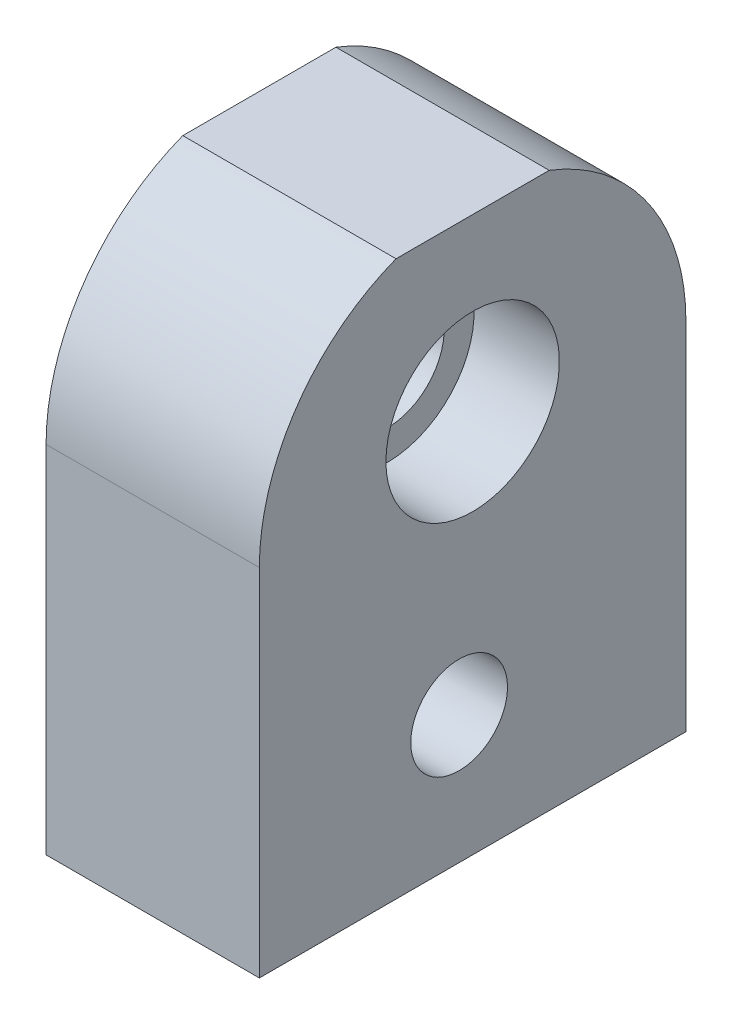
SolidWorks part; units mm, degrees
ref_plane "Front Plane" through (0, 0, 0) normal (0, 0, 1) x (1, 0, 0)
ref_plane "Top Plane" through (0, 0, 0) normal (0, 1, 0) x (1, 0, 0)
ref_plane "Right Plane" through (0, 0, 0) normal (1, 0, 0) x (0, 0, -1)
other "Configuration Table"
sketch "草图1" plane through (0, 0, 0) normal (0, 1, 0) x (1, 0, 0)
  line L0 (0, 0) -> (0, -30)
  line L1 (0, 0) -> (15, 0)
  line L2 (15, 0) -> (15, -30)
  line L3 (15, -30) -> (0, -30)
extrude "凸台-拉伸1" add sketch "草图1" along normal blind 25 contours L3 L0 L1 L2
sketch "草图3" plane through (0, 0, 0) normal (-1, 0, 0) x (0, 0, 1)
  line L0 (15, 25) -> (15, 0) construction
  line L1 (0, 25) -> (30, 25) construction
  line L2 (0, 0) -> (30, 0) construction
  line L7 (0, 25) -> (30, 25)
  circle A2 centre (15, 25) radius 15
  line M7 (30, 25) -> (0, 25)
  dimension "D1" = 0
extrude "凸台-拉伸3" add sketch "草图3" against normal blind 15 contours A2 L7 M7 region at (0, 31.3662, 15)
sketch "草图4" plane through (0, 0, 0) normal (0, -1, 0) x (1, 0, 0)
  line L0 (7.5, 30) -> (7.5, 0) construction
  line L1 (15, 30) -> (0, 30) construction
  line L2 (0, 0) -> (15, 0) construction
  circle A1 centre (7.5, 24) radius 1.65
  circle A2 centre (7.5, 6) radius 1.65
  dimension "D1" = 6
  dimension "D2" = 6
extrude "切除-拉伸2" cut sketch "草图4" against normal blind 10 contours L0 A1 | A1 L0 | L0 A2 | A2 L0 region at (8.2003, 0, 24) region at (8.2003, 0, 6) region at (6.7997, 0, 6) region at (6.7997, 0, 24)
sketch "草图5" plane through (0, 0, 0) normal (-1, 0, 0) x (0, 0, 1)
  line L0 (0, 0) -> (30, 0) construction
  line L4 (0, 25) -> (0, 0) construction
  circle A0 centre (15.95, 9) radius 3.4
  dimension "D2" = 6.8
  dimension "D1" = 9
  dimension "D3" = 15.95
sketch "草图9" plane through (0, 0, 0) normal (-1, 0, 0) x (0, 0, 1)
  line L0 (15, 27) -> (15, 40) construction
  circle A0 centre (15, 27) radius 6.1
  arc A1 (30, 25) -> (0, 25) centre (15, 25) ccw construction
  dimension "D1" = 12.2
extrude "切除-拉伸3" cut sketch "草图9" against normal blind 6
sketch "草图10" plane through (6, 0, 0) normal (-1, 0, 0) x (0, 0, 1)
  circle A0 centre (15, 27) radius 4
  dimension "D1" = 8
extrude "切除-拉伸4" cut sketch "草图10" against normal through all contours A0
mirror "镜向1" about plane through (0, 0, 0) normal (1, 0, 0) of bodies 109 110
delete or keep bodies "实体-删除/保留 1" type delete bodies bodies 109
sketch "草图12" plane through (0, 0, 0) normal (1, 0, 0) x (0, 0, -1)
  line L0 (-15, 25) -> (-15, 39) construction
  line L1 (-20.3852, 39) -> (-9.6148, 39)
  arc A0 (0, 25) -> (-30, 25) centre (-15, 25) ccw construction
  point P9 (-15, 39)
  arc M7 (0, 25) -> (-30, 25) centre (-15, 25) ccw
extrude "切除-拉伸6" cut sketch "草图12" against normal through all and the other way through all contours L1 M7 region at (0, 39.4012, 15)
extrude "切除-拉伸8" cut sketch "草图5" along normal through all
